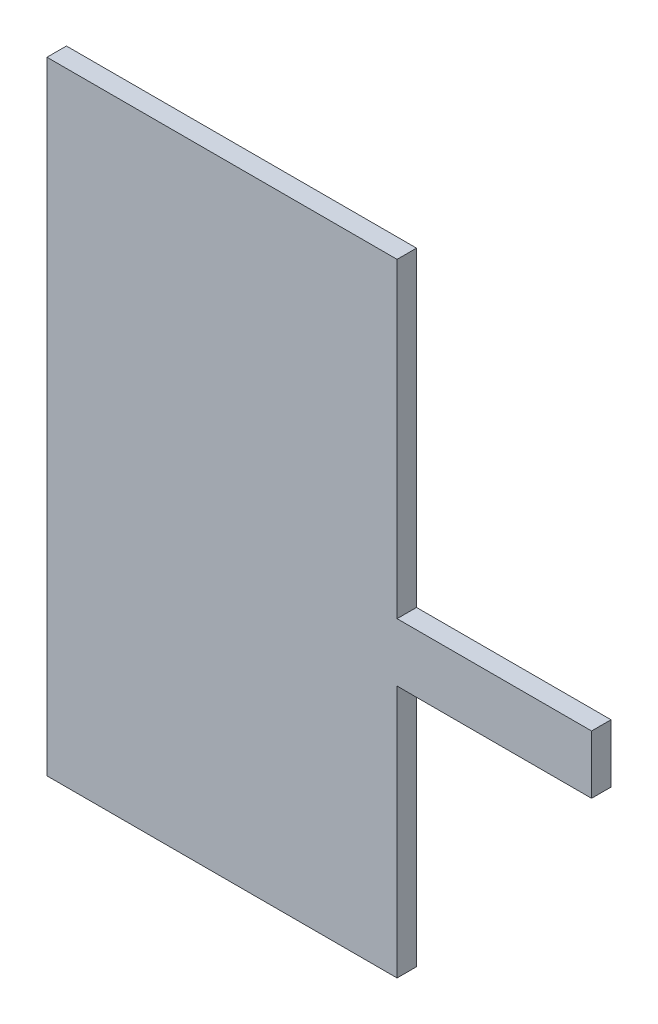
SolidWorks part; units mm, degrees
material "6061-T4 (SS)"
ref_plane "Front Plane" through (0, 0, 0) normal (0, 0, 1) x (1, 0, 0)
ref_plane "Top Plane" through (0, 0, 0) normal (0, 1, 0) x (1, 0, 0)
ref_plane "Right Plane" through (0, 0, 0) normal (1, 0, 0) x (0, 0, -1)
sketch "Sketch1" plane through (0, 0, 0) normal (0, 0, 1) x (1, 0, 0)
  line L3 (15.5494, 25) -> (29.7363, 25) construction
  line L6 (29.7363, -7) -> (11.7363, -7)
  line L7 (29.7363, 6) -> (39.7363, 6)
  line L8 (39.7363, 6) -> (39.7363, 9)
  line L9 (39.7363, 9) -> (29.7363, 9)
  line L10 (29.7363, -7) -> (29.7363, 6)
  line L11 (29.7363, 9) -> (29.7363, 25)
  line L12 (11.7363, -7) -> (11.7363, 25)
  line L13 (11.7363, 25) -> (29.7363, 25)
  point P1 (0, 0)
  point P3 (0, 0)
  point P4 (0, 0)
  dimension "D1" = 3
  dimension "D2" = 16
  dimension "D3" = 10
  dimension "D4" = 18
  dimension "D5" = 32
extrude "Boss-Extrude1" add sketch "Sketch1" along normal blind 1
